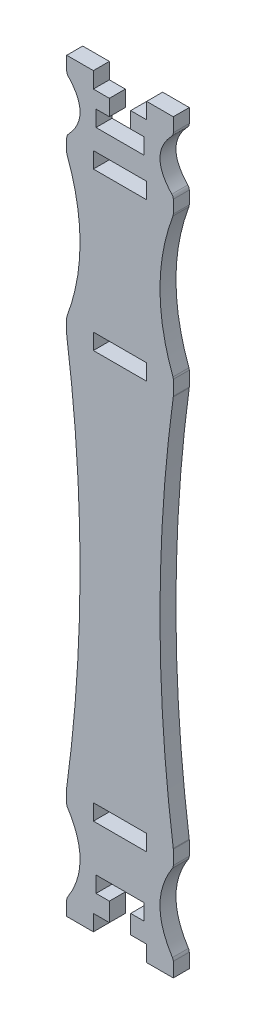
SolidWorks part; units mm, degrees
ref_plane "Alzado" through (0, 0, 0) normal (0, 0, 1) x (1, 0, 0)
ref_plane "Planta" through (0, 0, 0) normal (0, 1, 0) x (1, 0, 0)
ref_plane "Vista lateral" through (0, 0, 0) normal (1, 0, 0) x (0, 0, -1)
sketch "Croquis1" plane through (0, 0, 0) normal (0, 0, 1) x (1, 0, 0)
  line L0 (-15, -70) -> (-10, -70)
  line L1 (-10, 70) -> (-10, 67)
  line L2 (-7, 67) -> (-10, 67)
  line L3 (0, -70) -> (5, -70)
  line L4 (-15, 70) -> (-15, 67.4057)
  line L5 (0, -70) -> (0, -67)
  line L6 (-7, -63.5) -> (-7, -67)
  line L7 (-0.5, -60.5) -> (-9.5, -60.5)
  line L8 (-10, -67) -> (-10, -70)
  line L9 (-10, 70) -> (-15, 70)
  line L10 (-9.5, 61) -> (-0.5, 61)
  line L11 (-10, -52) -> (-10, -49)
  line L12 (-10, -52) -> (0, -52)
  line L13 (-0.5, -60.5) -> (-0.5, -63.5)
  line L14 (-0.5, -63.5) -> (-3, -63.5)
  line L15 (-10, -49) -> (0, -49)
  line L16 (0, -49) -> (0, -52)
  line L17 (-0.5, 61) -> (-0.5, 64)
  line L18 (-3, -63.5) -> (-3, -67)
  line L19 (-0.5, 64) -> (-3, 64)
  line L20 (-10, 27.5) -> (-10, 24.5)
  line L21 (-3, 64) -> (-3, 67)
  line L22 (-10, 24.5) -> (0, 24.5)
  line L23 (0, 24.5) -> (0, 27.5)
  line L24 (-7, 64) -> (-7, 67)
  line L25 (-15, 27.3187) -> (-15, 24.5677)
  line L26 (-9.5, -63.5) -> (-7, -63.5)
  line L27 (-9.5, -60.5) -> (-9.5, -63.5)
  line L28 (-7, -67) -> (-10, -67)
  line L29 (-9.5, 64) -> (-7, 64)
  line L30 (-9.5, 61) -> (-9.5, 64)
  line L31 (-10, 54) -> (-10, 57)
  line L32 (-10, 54) -> (0, 54)
  line L33 (-10, 57) -> (0, 57)
  line L34 (0, 57) -> (0, 54)
  line L35 (-3, 67) -> (0, 67)
  line L37 (0, 67) -> (0, 70)
  line L38 (5, 70) -> (0, 70)
  line L40 (0, 27.5) -> (-10, 27.5)
  line L42 (-15, 56.5943) -> (-15, 54.1813)
  line L43 (0, -67) -> (-3, -67)
  line L46 (-15, -49.0677) -> (-15, -51.7014)
  line L48 (-15, -67.2986) -> (-15, -70)
  line L49 (5, -70) -> (5, -67.2986)
  line L51 (5, -51.7014) -> (5, -49.0677)
  line L53 (5, 24.5677) -> (5, 27.3187)
  line L55 (5, 54.1813) -> (5, 56.5943)
  line L57 (5, 67.4057) -> (5, 70)
  arc A0 (-14.8403, -66.7566) -> (-15, -67.2986) centre (-14, -67.2986) ccw
  arc A1 (5, -67.2986) -> (4.8403, -66.7566) centre (4, -67.2986) ccw
  arc A2 (4.8403, -52.2434) -> (5, -51.7014) centre (4, -51.7014) ccw
  arc A3 (-15, -51.7014) -> (-14.8403, -52.2434) centre (-14, -51.7014) ccw
  arc A4 (-14.9909, -48.9331) -> (-15, -49.0677) centre (-14, -49.0677) ccw
  arc A5 (5, -49.0677) -> (4.9909, -48.9331) centre (4, -49.0677) ccw
  arc A6 (-15, 24.5677) -> (-14.9909, 24.4331) centre (-14, 24.5677) ccw
  arc A7 (4.9909, 24.4331) -> (5, 24.5677) centre (4, 24.5677) ccw
  arc A8 (-14.9371, 27.6678) -> (-15, 27.3187) centre (-14, 27.3187) ccw
  arc A9 (5, 27.3187) -> (4.9371, 27.6678) centre (4, 27.3187) ccw
  arc A10 (-14.7272, 57.2807) -> (-15, 56.5943) centre (-14, 56.5943) ccw
  arc A11 (-15, 54.1813) -> (-14.9371, 53.8322) centre (-14, 54.1813) ccw
  arc A12 (4.9371, 53.8322) -> (5, 54.1813) centre (4, 54.1813) ccw
  arc A13 (5, 56.5943) -> (4.7272, 57.2807) centre (4, 56.5943) ccw
  arc A14 (4.7272, 66.7193) -> (5, 67.4057) centre (4, 67.4057) ccw
  arc A15 (-15, 67.4057) -> (-14.7272, 66.7193) centre (-14, 67.4057) ccw
  spline S0 degree 3 poles (4.7272, 66.7193) (3.2424, 65.1462) (1.7576, 62) (3.2424, 58.8538) (4.7272, 57.2807) knots 0.028065 0.028065 0.028065 0.028065 0.5 0.971935 0.971935 0.971935 0.971935
  spline S1 degree 3 poles (-14.7272, 57.2807) (-13.2424, 58.8538) (-11.7576, 62) (-13.2424, 65.1462) (-14.7272, 66.7193) knots 0.028065 0.028065 0.028065 0.028065 0.5 0.971935 0.971935 0.971935 0.971935
  spline S2 degree 3 poles (-14.9371, 53.8322) (-13.3124, 49.4715) (-11.6876, 40.75) (-13.3124, 32.0285) (-14.9371, 27.6678) knots 0.006333 0.006333 0.006333 0.006333 0.5 0.993667 0.993667 0.993667 0.993667
  spline S3 degree 3 poles (4.9371, 53.8322) (3.3124, 49.4715) (1.6876, 40.75) (3.3124, 32.0285) (4.9371, 27.6678) knots 0.006333 0.006333 0.006333 0.006333 0.5 0.993667 0.993667 0.993667 0.993667
  spline S4 degree 3 poles (-14.9909, -48.9331) (-13.3303, -36.7054) (-11.6697, -12.25) (-13.3303, 12.2054) (-14.9909, 24.4331) knots 0.00091 0.00091 0.00091 0.00091 0.5 0.99909 0.99909 0.99909 0.99909
  spline S5 degree 3 poles (4.8403, -66.7566) (3.2801, -64.3377) (1.7199, -59.5) (3.2801, -54.6623) (4.8403, -52.2434) knots 0.016229 0.016229 0.016229 0.016229 0.5 0.983771 0.983771 0.983771 0.983771
  spline S6 degree 3 poles (-14.8403, -66.7566) (-13.2801, -64.3377) (-11.7199, -59.5) (-13.2801, -54.6623) (-14.8403, -52.2434) knots 0.016229 0.016229 0.016229 0.016229 0.5 0.983771 0.983771 0.983771 0.983771
  spline S7 degree 3 poles (4.9909, -48.9331) (3.3303, -36.7054) (1.6697, -12.25) (3.3303, 12.2054) (4.9909, 24.4331) knots 0.00091 0.00091 0.00091 0.00091 0.5 0.99909 0.99909 0.99909 0.99909
  dimension "D1" = 1
extrude "Saliente-Extruir1" add sketch "Croquis1" along normal blind 3 contours L38 | L38 L37 L1 L9 L0 L8 L28 L6 L26 L27 L7 L13 L14 L18 L43 L5 L3 A6 A8 region at (-5, -0.2365, 0)
